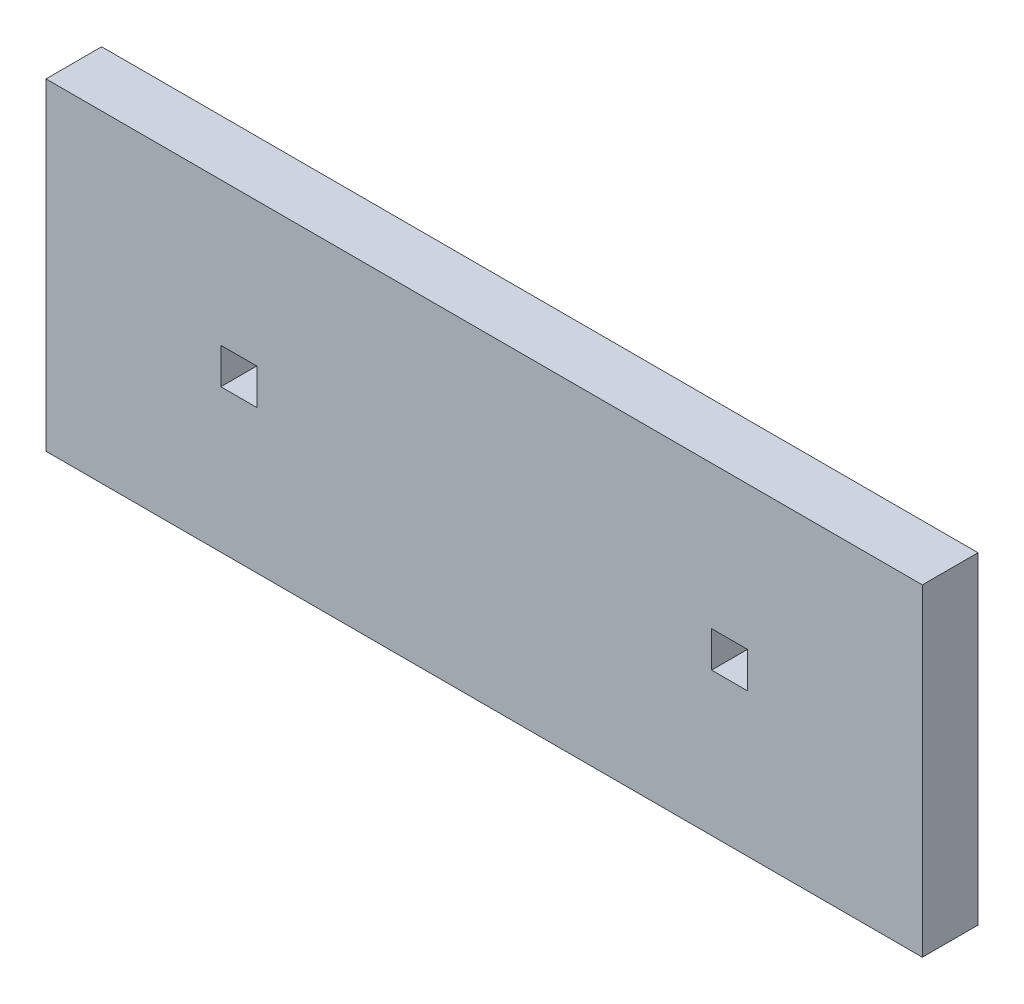
SolidWorks part; units mm, degrees
material "Acrylic (Medium-high impact)"
ref_plane "Front Plane" through (0, 0, 0) normal (0, 0, 1) x (1, 0, 0)
ref_plane "Top Plane" through (0, 0, 0) normal (0, 1, 0) x (1, 0, 0)
ref_plane "Right Plane" through (0, 0, 0) normal (1, 0, 0) x (0, 0, -1)
sketch "Sketch2" plane through (0, 0, 0) normal (0, 0, 1) x (1, 0, 0)
  line L0 (-12.975, -1.5875) -> (12.975, -1.5875) construction
  line L1 (25, -10.7875) -> (-25, -10.7875)
  line L2 (25, -10.7875) -> (25, 10.7875)
  line L3 (25, 10.7875) -> (-25, 10.7875)
  line L4 (-25, -10.7875) -> (-25, 10.7875)
  line L5 (25, -10.7875) -> (-25, 10.7875) construction
  line L6 (25, 10.7875) -> (-25, -10.7875) construction
  line L7 (-15.025, -0.5625) -> (-12.975, -0.5625)
  line L8 (-15.025, -0.5625) -> (-15.025, -2.6125)
  line L9 (-15.025, -2.6125) -> (-12.975, -2.6125)
  line L10 (-12.975, -0.5625) -> (-12.975, -2.6125)
  line L11 (15.025, -2.6125) -> (12.975, -2.6125)
  line L12 (15.025, -2.6125) -> (15.025, -0.5625)
  line L13 (15.025, -0.5625) -> (12.975, -0.5625)
  line L14 (12.975, -2.6125) -> (12.975, -0.5625)
  line L15 (-18, 10.7875) -> (-18, -10.7875) construction
  line L16 (0, -1.6485) -> (0, 1.6485) construction
  line L17 (22.5, 10.7875) -> (20.5, 10.7875)
  line L22 (-25, 10.7875) -> (-18, 10.7875)
  line L23 (-25, 10.7875) -> (-25, 7.6125)
  line L24 (-25, 7.6125) -> (-18, 7.6125)
  line L25 (-18, 10.7875) -> (-18, 7.6125)
  line L26 (-22.5, 7.6125) -> (-20.5, 7.6125)
  line L27 (-22.5, 7.6125) -> (-22.5, 10.7875)
  line L28 (-22.5, 10.7875) -> (-20.5, 10.7875)
  line L29 (-20.5, 7.6125) -> (-20.5, 10.7875)
  line L30 (20.5, 7.6125) -> (20.5, 10.7875)
  line L31 (22.5, 7.6125) -> (20.5, 7.6125)
  line L32 (22.5, 7.6125) -> (22.5, 10.7875)
  line L33 (25, 7.6125) -> (18, 7.6125)
  line L34 (18, 10.7875) -> (18, 7.6125)
  line L35 (25, 10.7875) -> (18, 10.7875)
  line L36 (25, 10.7875) -> (25, 7.6125)
  line L42 (-18, 10.7875) -> (18, 10.7875)
  line L43 (-18, 10.7875) -> (-18, 7.6125)
  line L44 (-18, 7.6125) -> (18, 7.6125)
  line L45 (18, 10.7875) -> (18, 7.6125)
  line L46 (-25, -1) -> (-28.175, -1)
  line L47 (-25, -1) -> (-25, 1)
  line L48 (-25, 1) -> (-28.175, 1)
  line L49 (-28.175, -1) -> (-28.175, 1)
  line L50 (25, -1) -> (28.175, -1)
  line L51 (25, -1) -> (25, 1)
  line L52 (25, 1) -> (28.175, 1)
  line L53 (28.175, -1) -> (28.175, 1)
  point P0 (0, 0)
  point P16 (0, -1.5875)
  point P29 (-21.5, 7.6125)
  point P30 (-21.5, 7.6125)
  point P32 (-22.5, 9.2)
  point P40 (-14, -0.5625)
  point P41 (14, -0.5625)
  point P42 (-15.025, -1.5875)
  point P49 (28.175, 0)
  point P50 (-28.175, 0)
  dimension "D1" = 2.05
  dimension "D3" = 50
  dimension "D6" = 7
  dimension "D7" = 2
  dimension "D8" = 3.175
  dimension "D4" = 28
  dimension "D5" = 9.2
  dimension "D9" = 2
  dimension "D10" = 3.175
  dimension "D2" = 18.4
extrude "Boss-Extrude1" add sketch "Sketch2" along normal blind 3.175 contours L34 L3 L25 L24 L4 L1 L2 L33 L31 L7 L10 L9 L8 L11 L14 L13 L12 region at (0, -1.5875, 0)
equation "\"bottomThickness\"= .220in"
equation "\"wallThickness\"= .125in"
equation "\"D10@Sketch2\"=\"wallThickness\""
equation "\"D8@Sketch2\"=\"wallThickness\""
equation "\"D1@Boss-Extrude1\"=\"wallThickness\""
